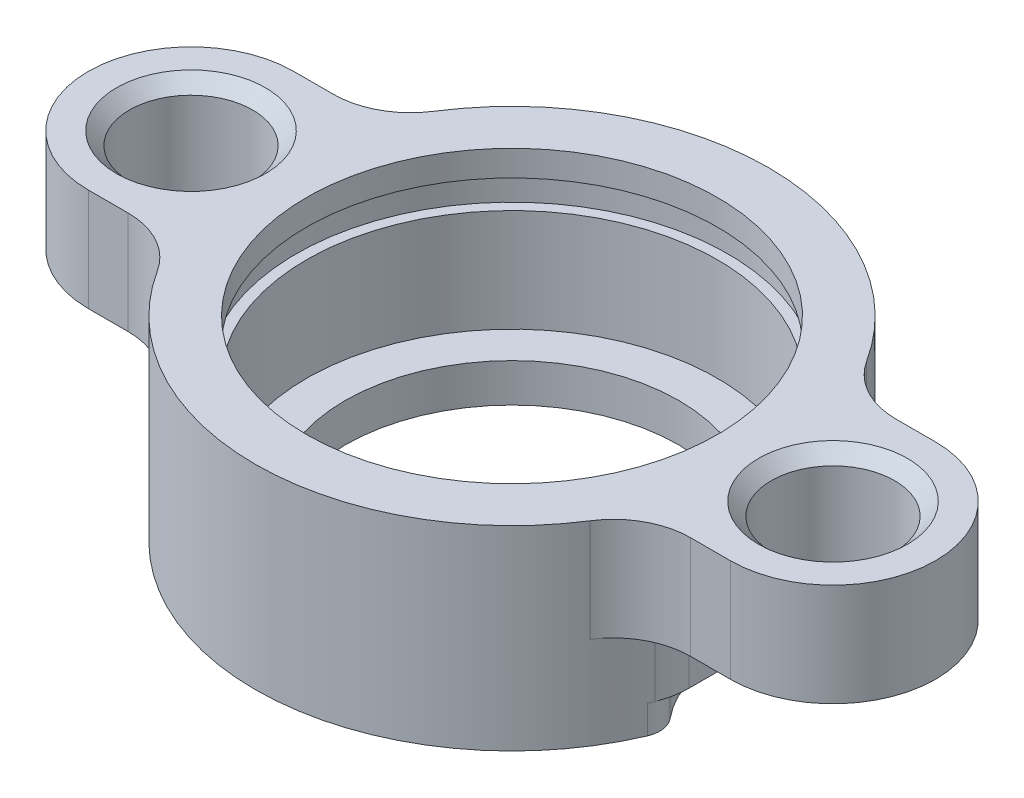
SolidWorks part; units mm, degrees
ref_plane "Plan de face" through (0, 0, 0) normal (0, 0, 1) x (1, 0, 0)
ref_plane "Plan de dessus" through (0, 0, 0) normal (0, 1, 0) x (1, 0, 0)
ref_plane "Plan de droite" through (0, 0, 0) normal (1, 0, 0) x (0, 0, -1)
sketch "Esquisse1" plane through (0, 0, 0) normal (0, 0, 1) x (1, 0, 0)
  line L0 (0, 6.6086) -> (0, -5.0424) construction
  line L1 (-6.5, -4) -> (-6.5, -5.5)
  line L2 (-6.5, -5.5) -> (-10, -5.5)
  line L3 (-10, -5.5) -> (-10, 2.1)
  line L4 (-10, 2.1) -> (-8, 2.1)
  line L5 (-8, 2.1) -> (-8, 1.1)
  line L6 (-8, 1.1) -> (-8.4, 1.1)
  line L7 (-8.4, 1.1) -> (-8.4, 0)
  line L8 (-8.4, 0) -> (-8, 0)
  line L9 (-8, 0) -> (-8, -4)
  line L10 (-8, -4) -> (-6.5, -4)
  dimension "D1" = 2
  dimension "D2" = 8
  dimension "D3" = 8.4
  dimension "D4" = 1.1
  dimension "D5" = 1.5
  dimension "D6" = 1.5
  dimension "D7" = 4
  dimension "D8" = 1
revolve "Révolution1" add sketch "Esquisse1" angle 360 about L0
sketch "Esquisse2" plane through (0, 2.1, 0) normal (0, 1, 0) x (1, 0, 0)
  line L0 (-12.5, -4) -> (-9.1652, -4)
  line L1 (-12.5, 4) -> (-9.1652, 4)
  line L2 (0, -4.18) -> (0, 4.18) construction
  line L5 (-9.5, -3.1225) -> (-9.5, 3.1225)
  circle A0 centre (-12.5, 0) radius 2.55 construction
  arc A1 (-12.5, 4) -> (-12.5, -4) centre (-12.5, 0) ccw
  circle A2 centre (0, 0) radius 10 construction
  arc A3 (-9.1652, 4) -> (-9.1652, -4) centre (0, 0) ccw
  circle A7 centre (-12.5, 0) radius 1.7 construction
  circle A11 centre (0, 0) radius 8 construction
  circle M6 centre (0, 0) radius 10
  dimension "D1" = 5.1
  dimension "D2" = 4
  dimension "D4" = 3.4
  dimension "D5" = 1.5
  dimension "D3" = 12.5
extrude "Boss.-Extru.1" add sketch "Esquisse2" against normal blind 4 contours L1 A1 L0 A0 M6 region at (-12.7463, 2.1, 0)
extrude "Enlèv. mat.-Extru.3" cut sketch "Esquisse2<6>" along normal up to surface (-4 mm away) from surface contours L5 M6 region at (-9.7004, 2.1, 0) up to face at (-12.0413, -1.9, 0) starting at face at (0, -5.5, 6.5)
sketch "Esquisse2<6>" plane through (0, 2.1, 0) normal (0, 1, 0) x (1, 0, 0) same geometry as "Esquisse2"
fillet "Congé2" radius 3 2 edges at (-9.5, -3.7, 3.1225) (-9.5, -3.7, -3.1225)
fillet "Congé3" radius 3 2 edges at (-9.1652, 0.1, -4) (-9.1652, 0.1, 4)
mirror "Symétrie1" about plane through (0, 0, 0) normal (1, 0, 0) of "Congé3", "Congé2", "Enlèv. mat.-Extru.3", "Boss.-Extru.1"
hole_wizard "Ø4.8 (4.8) Diameter Hole2" positions "Esquisse8" profile "Esquisse7" hole size "Ø4.8" standard "ANSI Metric"
sketch "Esquisse8" plane through (0, 2.1, 0) normal (0, 1, 0) x (1, 0, 0)
  point P0 (-12.5, 0)
  point P3 (12.5, 0)
sketch "Esquisse7" plane through (-12.5, 2.1, 0) normal (1, 0, 0) x (0, 0, 1)
  line L0 (0, 0) -> (0, 7.8421)
  line L1 (0, 7.8421) -> (2.4, 6.4)
  line L2 (2.4, 6.4) -> (2.4, 0)
  line L5 (2.4, 0) -> (0, 0)
  line L10 (0, 7.8421) -> (-2.4, 6.4) construction
  line L11 (0, -6.35) -> (0, 107.95) construction
  dimension "Hole Dia." = 4.8
  dimension "Hole Depth" = 6.4
  dimension "Drill Angle" = 118
chamfer "Chanfrein1" distance 0.5 angle 45 2 edges at (12.5, 2.1, 2.4) (-12.5, 2.1, 2.4)
sketch "Esquisse9" plane through (0, -5.5, 0) normal (0, -1, 0) x (1, 0, 0)
  circle A0 centre (-12.5, 0) radius 4.5
  circle A1 centre (12.5, 0) radius 4.5
  dimension "D1" = 9
extrude "Enlèv. mat.-Extru.4" cut sketch "Esquisse9" against normal blind 1.1
fillet "Congé4" radius 1 4 edges at (9.4211, -4.95, 3.2818) (9.4211, -4.95, -3.2818) (-9.4211, -4.95, 3.2818) (-9.4211, -4.95, -3.2818)
